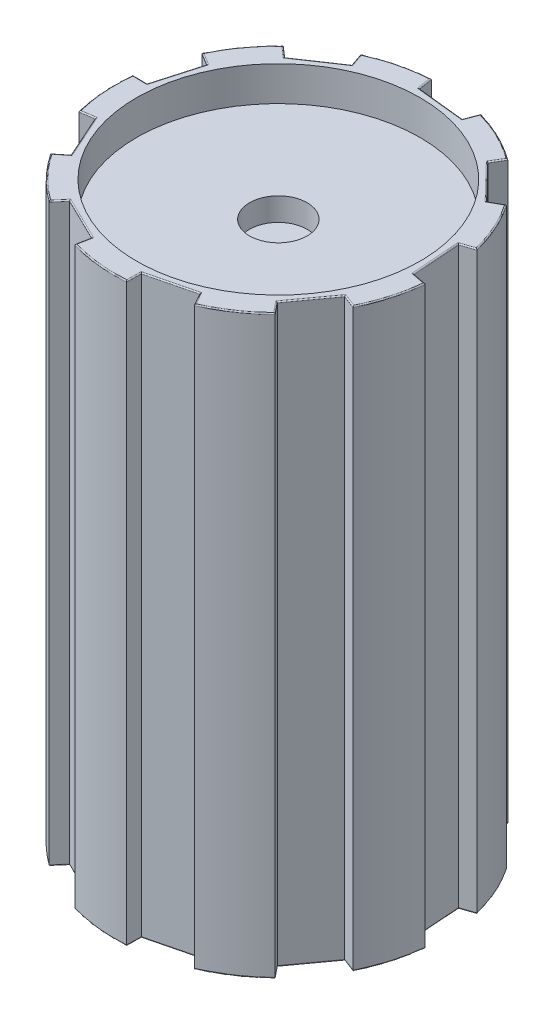
SolidWorks part; units mm, degrees
ref_plane "Front Plane" through (0, 0, 0) normal (0, 0, 1) x (1, 0, 0)
ref_plane "Top Plane" through (0, 0, 0) normal (0, 1, 0) x (1, 0, 0)
ref_plane "Right Plane" through (0, 0, 0) normal (1, 0, 0) x (0, 0, -1)
other "Configuration Table"
sketch "草图1" plane through (0, 0, 0) normal (0, 1, 0) x (1, 0, 0)
  circle A0 centre (0, 0) radius 13
  dimension "D1" = 26
extrude "凸台-拉伸1" add sketch "草图1" along normal blind 50
sketch "草图6" plane through (0, 50, 0) normal (0, 1, 0) x (1, 0, 0)
  circle A0 centre (0, 0) radius 14.25
  dimension "D1" = 28.5
extrude "凸台-拉伸4" add sketch "草图6" against normal through all
sketch "草图2" plane through (0, 50, 0) normal (0, 1, 0) x (1, 0, 0)
  circle A0 centre (0, 0) radius 12
  dimension "D1" = 24
extrude "切除-拉伸1" cut sketch "草图2" against normal blind 3
sketch "草图7" plane through (0, 50, 0) normal (0, 1, 0) x (1, 0, 0)
  line L0 (-16.366, 8.3194) -> (-11.756, 5.5494)
  line L1 (-16.366, 8.3194) -> (-18.2877, 1.6175)
  line L2 (-11.756, 5.5494) -> (-12.9104, 1.5237)
  line L3 (-18.2877, 1.6175) -> (-12.9104, 1.5237)
  line L72 (-7.1895, 16.8929) -> (-5.4386, 11.8077)
  line L73 (-7.1895, 16.8929) -> (-12.9695, 12.9942)
  line L74 (-12.9695, 12.9942) -> (-8.9106, 9.4658)
  line L75 (-5.4386, 11.8077) -> (-8.9106, 9.4658)
  line L76 (5.3511, 17.562) -> (3.4237, 12.5411)
  line L77 (5.3511, 17.562) -> (-1.5827, 18.2908)
  line L78 (-1.5827, 18.2908) -> (-0.7414, 12.9788)
  line L79 (3.4237, 12.5411) -> (-0.7414, 12.9788)
  line L80 (15.3878, 10.0137) -> (10.6839, 7.4063)
  line L81 (15.3878, 10.0137) -> (10.5447, 15.0289)
  line L82 (10.5447, 15.0289) -> (7.7747, 10.4189)
  line L83 (10.6839, 7.4063) -> (7.7747, 10.4189)
  line L84 (18.2244, -2.2201) -> (12.9451, -1.1939)
  line L85 (18.2244, -2.2201) -> (17.7381, 4.7348)
  line L86 (17.7381, 4.7348) -> (12.6529, 2.9838)
  line L87 (12.9451, -1.1939) -> (12.6529, 2.9838)
  line L88 (12.5336, -13.4151) -> (9.149, -9.2355)
  line L89 (12.5336, -13.4151) -> (16.6316, -7.7748)
  line L90 (16.6316, -7.7748) -> (11.6107, -5.8474)
  line L91 (9.149, -9.2355) -> (11.6107, -5.8474)
  line L92 (0.9782, -18.333) -> (1.0721, -12.9557)
  line L93 (0.9782, -18.333) -> (7.743, -16.6464)
  line L94 (7.743, -16.6464) -> (5.1357, -11.9426)
  line L95 (1.0721, -12.9557) -> (5.1357, -11.9426)
  line L96 (-11.0349, -14.6727) -> (-7.5065, -10.6138)
  line L97 (-11.0349, -14.6727) -> (-4.7686, -17.729)
  line L98 (-4.7686, -17.729) -> (-3.7424, -12.4497)
  line L99 (-7.5065, -10.6138) -> (-3.7424, -12.4497)
  line L100 (-17.8847, -4.1469) -> (-12.5727, -3.3055)
  line L101 (-17.8847, -4.1469) -> (-15.0489, -10.516)
  line L102 (-15.0489, -10.516) -> (-10.8693, -7.1315)
  line L103 (-12.5727, -3.3055) -> (-10.8693, -7.1315)
  circle A0 centre (0, 0) radius 13 construction
  point P41 (0, 0)
  point P78 (0, 0)
  point P150 (0, 0)
  dimension "D1" = 26
  dimension "D2" = 105
  dimension "D3" = 105
  dimension "D4" = 9
extrude "切除-拉伸2" cut sketch "草图7" against normal through all
sketch "草图8" plane through (0, 47, 0) normal (0, 1, 0) x (1, 0, 0)
  circle A0 centre (0, 0) radius 2.5
  dimension "D1" = 5
extrude "切除-拉伸3" cut sketch "草图8" against normal blind 2
fillet "圆角6" radius 0.1 36 edges at (-13.5382, 0, -1.5346) (-12.3332, 0, -3.5365) (-12.2942, 0, -5.8728) (-11.5285, 0, -8.376) (-14.2153, 0, 0.994) (12.799, 0, -0.895) (13.2466, 0, -3.1883) (-3.8622, 0, 13.066) (-1.4896, 0, 14.1719) (1.0611, 0, 13.5835) (3.1039, 0, 12.4491) (5.4401, 0, 12.4917) (7.9685, 0, 11.8138) (9.5442, 0, 9.7235) (10.3799, 0, 7.5415) (12.1968, 0, 6.0724) (13.698, 0, 3.9279) (13.5614, 0, 1.3137) (13.018, 0, -5.796) (11.2331, 0, -7.7107) (9.2293, 0, -8.9126) (8.0981, 0, -10.9571) (6.2468, 0, -12.8078) (3.6487, 0, -13.1272) (1.3412, 0, -12.76) (-0.8396, 0, -13.599) (-3.4473, 0, -13.8267) (-5.643, 0, -12.4014) (-7.1746, 0, -10.6368) (-9.3844, 0, -9.8778) (-13.1929, 0, 3.4038) (-11.721, 0, 5.2185) (-11.3573, 0, 7.5266) (-10.2506, 0, 9.8989) (-7.9184, 0, 11.0876) (-5.6244, 0, 11.5317)
fillet "圆角7" radius 0.1 37 edges at (0, 50, 12) (-12.2942, 50, -5.8728) (-12.3332, 50, -3.5365) (-13.5382, 50, -1.5346) (13.2466, 50, -3.1883) (12.799, 50, -0.895) (-14.2153, 50, 0.994) (-11.5285, 50, -8.376) (-10.2506, 50, 9.8989) (-11.3573, 50, 7.5266) (-11.721, 50, 5.2185) (-13.1929, 50, 3.4038) (-9.3844, 50, -9.8778) (-7.1746, 50, -10.6368) (-5.643, 50, -12.4014) (-3.4473, 50, -13.8267) (-0.8396, 50, -13.599) (1.3412, 50, -12.76) (3.6487, 50, -13.1272) (6.2468, 50, -12.8078) (8.0981, 50, -10.9571) (9.2293, 50, -8.9126) (11.2331, 50, -7.7107) (13.018, 50, -5.796) (13.5614, 50, 1.3137) (13.698, 50, 3.9279) (12.1968, 50, 6.0724) (10.3799, 50, 7.5415) (9.5442, 50, 9.7235) (7.9685, 50, 11.8138) (5.4401, 50, 12.4917) (3.1039, 50, 12.4491) (1.0611, 50, 13.5835) (-1.4896, 50, 14.1719) (-3.8622, 50, 13.066) (-5.6244, 50, 11.5317) (-7.9184, 50, 11.0876)
sketch "草图9" plane through (0, 47, 0) normal (0, 1, 0) x (1, 0, 0)
  circle A4 centre (0, 0) radius 12.3
  dimension "D1" = 24.6
extrude "切除-拉伸4" cut sketch "草图9" along normal through all
